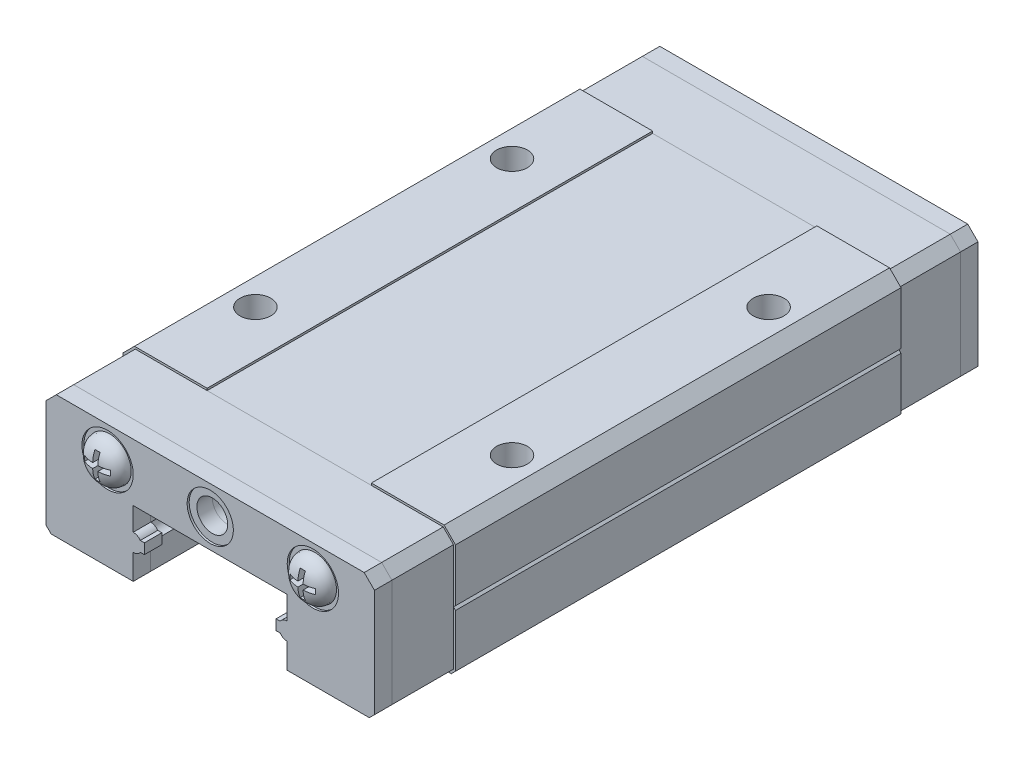
SolidWorks part; units mm, degrees
ref_plane "Front" through (0, 0, 0) normal (0, 0, 1) x (1, 0, 0)
ref_plane "Top" through (0, 0, 0) normal (0, 1, 0) x (1, 0, 0)
ref_plane "Right" through (0, 0, 0) normal (1, 0, 0) x (0, 0, -1)
sketch "Sketch1" plane through (0, 0, 0) normal (0, 0, 1) x (1, 0, 0)
  line L0 (15, 6) -> (-15, 6)
  line L1 (-16, -6) -> (16, -6) construction
  line L2 (-16, -6) -> (-16, 6) construction
  line L3 (-16, 6) -> (16, 6) construction
  line L4 (16, -6) -> (16, 6) construction
  line L5 (-16, -6) -> (16, 6) construction
  line L6 (-16, 6) -> (16, -6) construction
  line L7 (-16, 5) -> (-16, -5.5)
  line L8 (-15.5, -6) -> (-7.5, -6)
  line L9 (-7.5, -6) -> (-7.5, -3.55)
  line L10 (-7.5, 0.4) -> (7.5, 0.4)
  line L11 (-7.5, -1.85) -> (-7.5, 0.4)
  line L12 (0, 0) -> (0, 6) construction
  line L13 (16, -6) -> (16, 6) construction
  line L14 (-6.4126, -2.2) -> (-6.8126, -2.2)
  line L15 (-6.4126, -2.2) -> (-6.4126, -3.2)
  line L16 (-6.4126, -3.2) -> (-6.8126, -3.2)
  line L17 (6.4126, -3.2) -> (6.8126, -3.2)
  line L18 (6.4126, -2.2) -> (6.4126, -3.2)
  line L19 (6.4126, -2.2) -> (6.8126, -2.2)
  line L20 (7.5, -1.85) -> (7.5, 0.4)
  line L21 (7.5, -6) -> (7.5, -3.55)
  line L22 (15.5, -6) -> (7.5, -6)
  line L23 (16, 5) -> (16, -5.5)
  line L24 (-15, 6) -> (-16, 5)
  line L25 (-16, -5.5) -> (-15.5, -6)
  line L26 (15, 6) -> (16, 5)
  line L27 (16, -5.5) -> (15.5, -6)
  arc A0 (-7.5, -3.55) -> (-6.8126, -3.2) centre (-7.5, -2.7) ccw
  arc A1 (-6.8126, -2.2) -> (-7.5, -1.85) centre (-7.5, -2.7) ccw
  arc A2 (6.8126, -2.2) -> (7.5, -1.85) centre (7.5, -2.7) cw
  arc A3 (7.5, -3.55) -> (6.8126, -3.2) centre (7.5, -2.7) cw
  point P0 (0, 0)
  point P26 (0, 0.4)
  dimension "D4" = 1.7
  dimension "D1" = 12
  dimension "D2" = 32
  dimension "D3" = 8.5
  dimension "D5" = 3.3
  dimension "D6" = 0.5
  dimension "D7" = 0.5
  dimension "D8" = 0.4
  dimension "D9" = 6.4
extrude "Boss-Extrude1" add sketch "Sketch1" along normal blind 1.7
sketch "Sketch2" plane through (0, 0, 0) normal (0, 0, -1) x (-1, 0, 0)
  line L20 (7.5, 0.4) -> (7.5, -1.85)
  line L21 (6.8126, -2.2) -> (6.4126, -2.2)
  line L22 (6.4126, -2.2) -> (6.4126, -3.2)
  line L23 (6.4126, -3.2) -> (6.8126, -3.2)
  line L24 (7.5, -3.55) -> (7.5, -6)
  line L25 (7.5, -6) -> (15.5, -6)
  line L26 (15.5, -6) -> (16, -5.5)
  line L27 (16, -5.5) -> (16, 5)
  line L28 (16, 5) -> (15, 6)
  line L29 (15, 6) -> (-15, 6)
  line L30 (-15, 6) -> (-16, 5)
  line L31 (-16, 5) -> (-16, -5.5)
  line L32 (-16, -5.5) -> (-15.5, -6)
  line L33 (-15.5, -6) -> (-7.5, -6)
  line L34 (-7.5, -6) -> (-7.5, -3.55)
  line L35 (-6.8126, -3.2) -> (-6.4126, -3.2)
  line L36 (-6.4126, -3.2) -> (-6.4126, -2.2)
  line L37 (-6.4126, -2.2) -> (-6.8126, -2.2)
  line L38 (-7.5, -1.85) -> (-7.5, 0.4)
  line L39 (-7.5, 0.4) -> (7.5, 0.4)
  line L40 (7.5, 0.4) -> (7.5, -1.85)
  line L41 (6.8126, -2.2) -> (6.4126, -2.2)
  line L42 (6.4126, -2.2) -> (6.4126, -3.2)
  line L43 (6.4126, -3.2) -> (6.8126, -3.2)
  line L44 (7.5, -3.55) -> (7.5, -6)
  line L45 (7.5, -6) -> (15.5, -6)
  line L46 (15.5, -6) -> (16, -5.5)
  line L47 (16, -5.5) -> (16, 5)
  line L48 (16, 5) -> (15, 6)
  line L49 (15, 6) -> (-15, 6)
  line L50 (-15, 6) -> (-16, 5)
  line L51 (-16, 5) -> (-16, -5.5)
  line L52 (-16, -5.5) -> (-15.5, -6)
  line L53 (-15.5, -6) -> (-7.5, -6)
  line L54 (-7.5, -6) -> (-7.5, -3.55)
  line L55 (-6.8126, -3.2) -> (-6.4126, -3.2)
  line L56 (-6.4126, -3.2) -> (-6.4126, -2.2)
  line L57 (-6.4126, -2.2) -> (-6.8126, -2.2)
  line L58 (-7.5, -1.85) -> (-7.5, 0.4)
  line L59 (-7.5, 0.4) -> (7.5, 0.4)
  circle A0 centre (-7.5, -2.7) radius 0.85
  circle A1 centre (7.5, -2.7) radius 0.85
  arc A4 (7.5, -1.85) -> (6.8126, -2.2) centre (7.5, -2.7) ccw
  arc A5 (6.8126, -3.2) -> (7.5, -3.55) centre (7.5, -2.7) ccw
  arc A6 (-7.5, -3.55) -> (-6.8126, -3.2) centre (-7.5, -2.7) ccw
  arc A7 (-6.8126, -2.2) -> (-7.5, -1.85) centre (-7.5, -2.7) ccw
  arc A8 (7.5, -1.85) -> (6.8126, -2.2) centre (7.5, -2.7) ccw
  arc A9 (6.8126, -3.2) -> (7.5, -3.55) centre (7.5, -2.7) ccw
  arc A10 (-7.5, -3.55) -> (-6.8126, -3.2) centre (-7.5, -2.7) ccw
  arc A11 (-6.8126, -2.2) -> (-7.5, -1.85) centre (-7.5, -2.7) ccw
  line M25 (7.5, 0.4) -> (7.5, -1.85)
  line M31 (7.5, -3.55) -> (7.5, -6)
  line M32 (7.5, -6) -> (15.5, -6)
  line M33 (15.5, -6) -> (16, -5.5)
  line M34 (16, -5.5) -> (16, 5)
  line M35 (16, 5) -> (15, 6)
  line M36 (15, 6) -> (-15, 6)
  line M37 (-15, 6) -> (-16, 5)
  line M38 (-16, 5) -> (-16, -5.5)
  line M39 (-16, -5.5) -> (-15.5, -6)
  line M40 (-15.5, -6) -> (-7.5, -6)
  line M41 (-7.5, -6) -> (-7.5, -3.55)
  line M47 (-7.5, -1.85) -> (-7.5, 0.4)
  line M48 (-7.5, 0.4) -> (7.5, 0.4)
  dimension "D1" = 0
extrude "Boss-Extrude2" add sketch "Sketch2" along normal blind 6 separate body contours A1 A0 M31 M32 M33 M34 M35 M36 M37 M38 M39 M40 M41 M47 M48 M25 region at (0, 0.9516, 0)
sketch "Sketch3" plane through (0, 0, -6) normal (0, 0, -1) x (-1, 0, 0)
  line L14 (-7.5, -6) -> (-15.7828, -6)
  line L15 (-7.5, -6) -> (15.7828, -6)
  line L16 (7.5, -3.55) -> (7.5, -6) construction
  line L17 (7.5, 0.4) -> (7.5, -1.85) construction
  line L18 (-7.5, 0.4) -> (7.5, 0.4) construction
  line L19 (-7.5, -1.85) -> (-7.5, 0.4) construction
  line L20 (-7.5, -6) -> (-7.5, -3.55) construction
  line L21 (7.5, -3.55) -> (7.5, -6)
  line L22 (7.5, 0.4) -> (7.5, -1.85)
  line L23 (-7.5, 0.4) -> (7.5, 0.4)
  line L24 (-7.5, -1.85) -> (-7.5, 0.4)
  line L25 (-7.5, -6) -> (-7.5, -3.55)
  line L28 (7.3, -3.3185) -> (7.3, -6.2)
  line L29 (7.3, -6.2) -> (15.5828, -6.2)
  line L30 (15.5828, -6.2) -> (16.2, -5.5828)
  line L31 (16.2, -5.5828) -> (16.2, 5.0828)
  line L32 (16.2, 5.0828) -> (15.0828, 6.2)
  line L33 (15.0828, 6.2) -> (-15.0828, 6.2)
  line L34 (-15.0828, 6.2) -> (-16.2, 5.0828)
  line L35 (-16.2, 5.0828) -> (-16.2, -5.5828)
  line L36 (-16.2, -5.5828) -> (-15.5828, -6.2)
  line L37 (-15.5828, -6.2) -> (-7.3, -6.2)
  line L38 (-7.3, -6.2) -> (-7.3, -3.3185)
  line L39 (-7.3, -2.0815) -> (-7.3, 0.2)
  line L40 (-7.3, 0.2) -> (7.3, 0.2)
  line L41 (7.3, 0.2) -> (7.3, -2.0815)
  line L42 (7.3, -3.3185) -> (7.3, -6.2)
  line L43 (7.3, -6.2) -> (15.5828, -6.2)
  line L44 (15.5828, -6.2) -> (16.2, -5.5828)
  line L45 (16.2, -5.5828) -> (16.2, 5.0828)
  line L46 (16.2, 5.0828) -> (15.0828, 6.2)
  line L47 (15.0828, 6.2) -> (-15.0828, 6.2)
  line L48 (-15.0828, 6.2) -> (-16.2, 5.0828)
  line L49 (-16.2, 5.0828) -> (-16.2, -5.5828)
  line L50 (-16.2, -5.5828) -> (-15.5828, -6.2)
  line L51 (-15.5828, -6.2) -> (-7.3, -6.2)
  line L52 (-7.3, -6.2) -> (-7.3, -3.3185)
  line L53 (-7.3, -2.0815) -> (-7.3, 0.2)
  line L54 (-7.3, 0.2) -> (7.3, 0.2)
  line L55 (7.3, 0.2) -> (7.3, -2.0815)
  circle A2 centre (-7.5, -2.7) radius 0.85
  circle A3 centre (7.5, -2.7) radius 0.85
  arc A4 (7.3, -3.3185) -> (7.3, -2.0815) centre (7.5, -2.7) ccw
  arc A5 (-7.3, -2.0815) -> (-7.3, -3.3185) centre (-7.5, -2.7) ccw
  arc A6 (7.3, -3.3185) -> (7.3, -2.0815) centre (7.5, -2.7) ccw
  arc A7 (-7.3, -2.0815) -> (-7.3, -3.3185) centre (-7.5, -2.7) ccw
  arc M19 (7.5, -1.85) -> (7.5, -3.55) centre (7.5, -2.7) cw
  line M20 (7.5, -3.55) -> (7.5, -6)
  line M21 (7.5, -6) -> (15.5, -6)
  line M22 (15.5, -6) -> (16, -5.5)
  line M23 (16, -5.5) -> (16, 5)
  line M24 (16, 5) -> (15, 6)
  line M25 (15, 6) -> (-15, 6)
  line M26 (-15, 6) -> (-16, 5)
  line M27 (-16, 5) -> (-16, -5.5)
  line M28 (-16, -5.5) -> (-15.5, -6)
  line M29 (-15.5, -6) -> (-7.5, -6)
  line M30 (-7.5, -6) -> (-7.5, -3.55)
  arc M31 (-7.5, -3.55) -> (-7.5, -1.85) centre (-7.5, -2.7) cw
  line M32 (-7.5, -1.85) -> (-7.5, 0.4)
  line M33 (-7.5, 0.4) -> (7.5, 0.4)
  line M34 (7.5, 0.4) -> (7.5, -1.85)
  dimension "D1" = 0.2
extrude "Boss-Extrude3" add sketch "Sketch3" along normal blind 43.4 separate body contours M34 M19 M20 M21 M22 M23 M24 M25 M26 M27 M28 M29 M30 M31 M32 M33 | L49 L50 L14 L15 L44 L45 L46 L47 L48 M28 M27 M26 M25 M24 M23 M22 region at (0, 0.9516, -6) region at (15.6414, -5.9654, -6)
sketch "Sketch4" plane through (0, 0, -49.4) normal (0, 0, -1) x (-1, 0, 0)
  line L20 (7.5, 0.4) -> (7.5, -1.85)
  line L21 (6.8126, -2.2) -> (6.4126, -2.2)
  line L22 (6.4126, -2.2) -> (6.4126, -3.2)
  line L23 (6.4126, -3.2) -> (6.8126, -3.2)
  line L24 (7.5, -3.55) -> (7.5, -6)
  line L25 (7.5, -6) -> (15.5, -6)
  line L26 (15.5, -6) -> (16, -5.5)
  line L27 (16, -5.5) -> (16, 5)
  line L28 (16, 5) -> (15, 6)
  line L29 (15, 6) -> (-15, 6)
  line L30 (-15, 6) -> (-16, 5)
  line L31 (-16, 5) -> (-16, -5.5)
  line L32 (-16, -5.5) -> (-15.5, -6)
  line L33 (-15.5, -6) -> (-7.5, -6)
  line L34 (-7.5, -6) -> (-7.5, -3.55)
  line L35 (-6.8126, -3.2) -> (-6.4126, -3.2)
  line L36 (-6.4126, -3.2) -> (-6.4126, -2.2)
  line L37 (-6.4126, -2.2) -> (-6.8126, -2.2)
  line L38 (-7.5, -1.85) -> (-7.5, 0.4)
  line L39 (-7.5, 0.4) -> (7.5, 0.4)
  line L40 (7.5, 0.4) -> (7.5, -1.85)
  line L41 (6.8126, -2.2) -> (6.4126, -2.2)
  line L42 (6.4126, -2.2) -> (6.4126, -3.2)
  line L43 (6.4126, -3.2) -> (6.8126, -3.2)
  line L44 (7.5, -3.55) -> (7.5, -6)
  line L45 (7.5, -6) -> (15.5, -6)
  line L46 (15.5, -6) -> (16, -5.5)
  line L47 (16, -5.5) -> (16, 5)
  line L48 (16, 5) -> (15, 6)
  line L49 (15, 6) -> (-15, 6)
  line L50 (-15, 6) -> (-16, 5)
  line L51 (-16, 5) -> (-16, -5.5)
  line L52 (-16, -5.5) -> (-15.5, -6)
  line L53 (-15.5, -6) -> (-7.5, -6)
  line L54 (-7.5, -6) -> (-7.5, -3.55)
  line L55 (-6.8126, -3.2) -> (-6.4126, -3.2)
  line L56 (-6.4126, -3.2) -> (-6.4126, -2.2)
  line L57 (-6.4126, -2.2) -> (-6.8126, -2.2)
  line L58 (-7.5, -1.85) -> (-7.5, 0.4)
  line L59 (-7.5, 0.4) -> (7.5, 0.4)
  circle A0 centre (-7.5, -2.7) radius 0.85
  circle A1 centre (7.5, -2.7) radius 0.85
  arc A4 (7.5, -1.85) -> (6.8126, -2.2) centre (7.5, -2.7) ccw
  arc A5 (6.8126, -3.2) -> (7.5, -3.55) centre (7.5, -2.7) ccw
  arc A6 (-7.5, -3.55) -> (-6.8126, -3.2) centre (-7.5, -2.7) ccw
  arc A7 (-6.8126, -2.2) -> (-7.5, -1.85) centre (-7.5, -2.7) ccw
  arc A8 (7.5, -1.85) -> (6.8126, -2.2) centre (7.5, -2.7) ccw
  arc A9 (6.8126, -3.2) -> (7.5, -3.55) centre (7.5, -2.7) ccw
  arc A10 (-7.5, -3.55) -> (-6.8126, -3.2) centre (-7.5, -2.7) ccw
  arc A11 (-6.8126, -2.2) -> (-7.5, -1.85) centre (-7.5, -2.7) ccw
  dimension "D1" = 0
extrude "Boss-Extrude4" add sketch "Sketch4" along normal blind 6 separate body contours L49 L50 L51 L52 L53 L54 A10 L55 L56 L57 A11 L58 L59 L40 A8 L41 L42 L43 A9 L44 L45 L46 L47 L48
sketch "Sketch5" plane through (0, 0, -55.4) normal (0, 0, -1) x (-1, 0, 0)
  line L20 (7.5, 0.4) -> (7.5, -1.85)
  line L21 (-7.5, 0.4) -> (7.5, 0.4)
  line L22 (-7.5, -1.85) -> (-7.5, 0.4)
  line L23 (-6.4126, -2.2) -> (-6.8126, -2.2)
  line L24 (-6.4126, -3.2) -> (-6.4126, -2.2)
  line L25 (-6.8126, -3.2) -> (-6.4126, -3.2)
  line L26 (-7.5, -6) -> (-7.5, -3.55)
  line L27 (-15.5, -6) -> (-7.5, -6)
  line L28 (-16, -5.5) -> (-15.5, -6)
  line L29 (-16, 5) -> (-16, -5.5)
  line L30 (-15, 6) -> (-16, 5)
  line L31 (15, 6) -> (-15, 6)
  line L32 (16, 5) -> (15, 6)
  line L33 (16, -5.5) -> (16, 5)
  line L34 (15.5, -6) -> (16, -5.5)
  line L35 (7.5, -6) -> (15.5, -6)
  line L36 (7.5, -3.55) -> (7.5, -6)
  line L37 (6.4126, -3.2) -> (6.8126, -3.2)
  line L38 (6.4126, -2.2) -> (6.4126, -3.2)
  line L39 (6.8126, -2.2) -> (6.4126, -2.2)
  line L40 (7.5, 0.4) -> (7.5, -1.85)
  line L41 (-7.5, 0.4) -> (7.5, 0.4)
  line L42 (-7.5, -1.85) -> (-7.5, 0.4)
  line L43 (-6.4126, -2.2) -> (-6.8126, -2.2)
  line L44 (-6.4126, -3.2) -> (-6.4126, -2.2)
  line L45 (-6.8126, -3.2) -> (-6.4126, -3.2)
  line L46 (-7.5, -6) -> (-7.5, -3.55)
  line L47 (-15.5, -6) -> (-7.5, -6)
  line L48 (-16, -5.5) -> (-15.5, -6)
  line L49 (-16, 5) -> (-16, -5.5)
  line L50 (-15, 6) -> (-16, 5)
  line L51 (15, 6) -> (-15, 6)
  line L52 (16, 5) -> (15, 6)
  line L53 (16, -5.5) -> (16, 5)
  line L54 (15.5, -6) -> (16, -5.5)
  line L55 (7.5, -6) -> (15.5, -6)
  line L56 (7.5, -3.55) -> (7.5, -6)
  line L57 (6.4126, -3.2) -> (6.8126, -3.2)
  line L58 (6.4126, -2.2) -> (6.4126, -3.2)
  line L59 (6.8126, -2.2) -> (6.4126, -2.2)
  arc A4 (-6.8126, -2.2) -> (-7.5, -1.85) centre (-7.5, -2.7) ccw
  arc A5 (-7.5, -3.55) -> (-6.8126, -3.2) centre (-7.5, -2.7) ccw
  arc A6 (6.8126, -3.2) -> (7.5, -3.55) centre (7.5, -2.7) ccw
  arc A7 (7.5, -1.85) -> (6.8126, -2.2) centre (7.5, -2.7) ccw
  arc A8 (-6.8126, -2.2) -> (-7.5, -1.85) centre (-7.5, -2.7) ccw
  arc A9 (-7.5, -3.55) -> (-6.8126, -3.2) centre (-7.5, -2.7) ccw
  arc A10 (6.8126, -3.2) -> (7.5, -3.55) centre (7.5, -2.7) ccw
  arc A11 (7.5, -1.85) -> (6.8126, -2.2) centre (7.5, -2.7) ccw
  dimension "D1" = 0
extrude "Boss-Extrude5" add sketch "Sketch5" along normal blind 1.7 separate body
sketch "Sketch6" plane through (0, 0, -49.4) normal (0, 0, -1) x (-1, 0, 0)
  line L0 (-16.2, -0.25) -> (-16, -0.25) construction
  line L1 (-16.2, 5.0828) -> (-16.2, -5.5828) construction
  line L2 (-16, 5) -> (-16, -5.5) construction
  line L3 (-16, -0.25) -> (-16.2, -0.05)
  line L4 (-16, -0.25) -> (-16.2, -0.45)
  line L5 (-16.2, -0.05) -> (-16.2, -0.45)
  dimension "D1" = 45
extrude "Cut-Extrude3" cut sketch "Sketch6" against normal up to next (43.4 mm away)
sketch "Sketch8" plane through (0, 6.2, 0) normal (0, 1, 0) x (1, 0, 0)
  line L0 (-15.0828, 49.4) -> (15.0828, 49.4) construction
  line L1 (-8, 49.4) -> (8, 49.4)
  line L2 (-8, 49.4) -> (-8, 6)
  line L3 (-8, 6) -> (8, 6)
  line L4 (8, 49.4) -> (8, 6)
  line L5 (-8, 49.4) -> (8, 6) construction
  line L6 (-8, 6) -> (8, 49.4) construction
  line L7 (-15.0828, 6) -> (15.0828, 6) construction
  point P4 (0, 27.7)
  dimension "D1" = 16
extrude "Cut-Extrude4" cut sketch "Sketch8" against normal blind 0.2
mirror "Mirror1" about plane through (0, 0, 0) normal (1, 0, 0) of "Cut-Extrude3"
sketch "Sketch9" plane through (0, 6.2, 0) normal (0, 1, 0) x (1, 0, 0)
  line L1 (-16.2, 27.7) -> (16.2, 27.7) construction
  line L3 (-16.2, 49.4) -> (-16.2, 6) construction
  line L4 (16.2, 49.4) -> (16.2, 6) construction
  line L6 (-12.5, 15.2) -> (12.5, 15.2) construction
  line L7 (-12.5, 15.2) -> (-12.5, 40.2) construction
  line L8 (-12.5, 40.2) -> (12.5, 40.2) construction
  line L9 (12.5, 15.2) -> (12.5, 40.2) construction
  line L10 (-12.5, 15.2) -> (12.5, 40.2) construction
  line L11 (-12.5, 40.2) -> (12.5, 15.2) construction
  circle A4 centre (12.5, 40.2) radius 1.5
  circle A5 centre (-12.5, 40.2) radius 1.5
  circle A6 centre (-12.5, 15.2) radius 1.5
  circle A7 centre (12.5, 15.2) radius 1.5
  point P6 (0, 27.7)
  dimension "D1" = 25
  dimension "D3" = 3
  dimension "D4" = 3
  dimension "D5" = 3
  dimension "D2" = 3
extrude "Cut-Extrude5" cut sketch "Sketch9" against normal blind 5.8
sketch "Sketch10" plane through (0, 0, -57.1) normal (0, 0, -1) x (-1, 0, 0)
  line L0 (15, 6) -> (-15, 6) construction
  line L1 (-16, 5) -> (-16, -5.5) construction
  line L2 (16, -5.5) -> (16, 5) construction
  line L4 (0, 0.4) -> (0, 6) construction
  line L5 (-7.5, 0.4) -> (7.5, 0.4) construction
  line L6 (-8, 6) -> (8, 6) construction
  circle A0 centre (-10, 3) radius 2.5
  circle A1 centre (10, 3) radius 2.5
  circle A3 centre (0, 3.2) radius 2.25
  dimension "D1" = 5
  dimension "D4" = 5
  dimension "D5" = 6
  dimension "D7" = 4.5
  dimension "D2" = 3
  dimension "D3" = 6
  dimension "D6" = 3
extrude "Cut-Extrude6" cut sketch "Sketch10" against normal blind 0.2
sketch "Sketch11" plane through (0, 0, -56.9) normal (0, 0, -1) x (-1, 0, 0)
  circle A0 centre (0, 3.2) radius 1.5
  dimension "D1" = 3
extrude "Cut-Extrude7" cut sketch "Sketch11" against normal blind 5.8
sketch "Sketch12" plane through (0, 0, -56.9) normal (0, 0, -1) x (-1, 0, 0)
  circle A0 centre (-10, 3) radius 2.1
  dimension "D1" = 4.2
extrude "Boss-Extrude7" add sketch "Sketch12" along normal blind 1.4
fillet "Fillet1" radius 1.4 1 edges at (7.9, 3, -58.3) second distance 1.8 first distance on face at (7.9, 3, -58.3)
sketch "Sketch14" plane through (0, 0, -58.3) normal (0, 0, -1) x (-1, 0, 0)
  line L0 (-9.7, 3) -> (-10.3, 3) construction
  line L2 (-10.25, 1.75) -> (-9.75, 1.75)
  line L3 (-10.25, 1.75) -> (-10.25, 4.25)
  line L4 (-10.25, 4.25) -> (-9.75, 4.25)
  line L5 (-9.75, 1.75) -> (-9.75, 4.25)
  line L6 (-10.25, 1.75) -> (-9.75, 4.25) construction
  line L7 (-10.25, 4.25) -> (-9.75, 1.75) construction
  line L8 (-11.25, 2.75) -> (-8.75, 2.75)
  line L9 (-11.25, 2.75) -> (-11.25, 3.25)
  line L10 (-11.25, 3.25) -> (-8.75, 3.25)
  line L11 (-8.75, 2.75) -> (-8.75, 3.25)
  line L12 (-11.25, 2.75) -> (-8.75, 3.25) construction
  line L13 (-11.25, 3.25) -> (-8.75, 2.75) construction
  spline S1 degree 3 poles (-9.7156, 2.8822) (-9.6922, 3) (-9.7156, 3.1178) (-9.7823, 3.2177) (-9.8822, 3.2844) (-10, 3.3078) (-10.1178, 3.2844) (-10.2177, 3.2177) (-10.2844, 3.1178) (-10.3078, 3) (-10.2844, 2.8822) (-10.2177, 2.7823) (-10.1178, 2.7156) (-10, 2.6922) (-9.8822, 2.7156) (-9.7823, 2.7823) (-9.7156, 2.8822) (-9.6922, 3) (-9.7156, 3.1178) knots -0.1875 -0.125 -0.0625 0 0.0625 0.125 0.1875 0.25 0.3125 0.375 0.4375 0.5 0.5625 0.625 0.6875 0.75 0.8125 0.875 0.9375 1 1.0625 1.125 1.1875 only from (-9.7, 3) to (-9.7, 3)
  spline S2 degree 3 poles (-9.7156, 2.8822) (-9.6922, 3) (-9.7156, 3.1178) (-9.7823, 3.2177) (-9.8822, 3.2844) (-10, 3.3078) (-10.1178, 3.2844) (-10.2177, 3.2177) (-10.2844, 3.1178) (-10.3078, 3) (-10.2844, 2.8822) (-10.2177, 2.7823) (-10.1178, 2.7156) (-10, 2.6922) (-9.8822, 2.7156) (-9.7823, 2.7823) (-9.7156, 2.8822) (-9.6922, 3) (-9.7156, 3.1178) knots -0.1875 -0.125 -0.0625 0 0.0625 0.125 0.1875 0.25 0.3125 0.375 0.4375 0.5 0.5625 0.625 0.6875 0.75 0.8125 0.875 0.9375 1 1.0625 1.125 1.1875 only from (-9.7, 3) to (-9.7, 3) construction
  point P1 (-10, 3)
  point P7 (-10, 3)
  dimension "D2" = 2.5
  dimension "D3" = 0.5
  dimension "D4" = 0.5
  dimension "D5" = 2.5
  dimension "D1" = 0
extrude "Cut-Extrude8" cut sketch "Sketch14" against normal blind 1 contours L3 L8 | L8 | L8 L5 | L5 | L10 | L10 L5 | L10 L3 | L10 L3 L8 L5 | L3 | L10 L9 L8 L3 | L8 L11 L10 L5 | L3 L10 L5 L4 | L8 L3 L2 L5 region at (10, 2.239, -58.3) region at (10.761, 3, -58.3) region at (10.2238, 2.7762, -58.3) region at (9.7762, 2.7762, -58.3) region at (9.239, 3, -58.3) region at (10.2701, 3, -58.3) region at (10, 3, -58.3) region at (10, 2.7299, -58.3) region at (9.7299, 3, -58.3) region at (10.2238, 3.2238, -58.3) region at (9.7762, 3.2238, -58.3) region at (10, 3.761, -58.3) region at (10, 3.2701, -58.3)
mirror "Mirror2" about plane through (0, 0, 0) normal (1, 0, 0) of "Fillet1", "Cut-Extrude8", "Boss-Extrude7"
ref_plane "Plane1" through (0, 0, -27.7) normal (0, 0, -1) x (-1, 0, 0)
mirror "Mirror3" about plane through (0, 0, -27.7) normal (0, 0, -1) of "Cut-Extrude7", "Cut-Extrude6"
sketch "Sketch16" plane through (0, 0, 1.5) normal (0, 0, 1) x (1, 0, 0)
  circle A0 centre (10, 3) radius 2.1
  dimension "D1" = 4.2
extrude "Boss-Extrude8" add sketch "Sketch16" along normal blind 1.4
fillet "Fillet2" radius 1.4 1 edges at (12.1, 3, 2.9) second distance 1.8 first distance on face at (12.1, 3, 2.9)
sketch "Sketch17" plane through (0, 0, 2.9) normal (0, 0, 1) x (1, 0, 0)
  line L12 (10.25, 3.25) -> (10.25, 4.25)
  line L13 (11.25, 3.25) -> (10.25, 3.25)
  line L14 (11.25, 2.75) -> (11.25, 3.25)
  line L15 (10.25, 2.75) -> (11.25, 2.75)
  line L16 (10.25, 1.75) -> (10.25, 2.75)
  line L17 (9.75, 1.75) -> (10.25, 1.75)
  line L18 (9.75, 2.75) -> (9.75, 1.75)
  line L19 (8.75, 2.75) -> (9.75, 2.75)
  line L20 (8.75, 3.25) -> (8.75, 2.75)
  line L21 (9.75, 3.25) -> (8.75, 3.25)
  line L22 (9.75, 4.25) -> (9.75, 3.25)
  line L23 (10.25, 4.25) -> (9.75, 4.25)
  line L24 (10.25, 3.25) -> (10.25, 4.25)
  line L25 (11.25, 3.25) -> (10.25, 3.25)
  line L26 (11.25, 2.75) -> (11.25, 3.25)
  line L27 (10.25, 2.75) -> (11.25, 2.75)
  line L28 (10.25, 1.75) -> (10.25, 2.75)
  line L29 (9.75, 1.75) -> (10.25, 1.75)
  line L30 (9.75, 2.75) -> (9.75, 1.75)
  line L31 (8.75, 2.75) -> (9.75, 2.75)
  line L32 (8.75, 3.25) -> (8.75, 2.75)
  line L33 (9.75, 3.25) -> (8.75, 3.25)
  line L34 (9.75, 4.25) -> (9.75, 3.25)
  line L35 (10.25, 4.25) -> (9.75, 4.25)
  dimension "D1" = 0
extrude "Cut-Extrude9" cut sketch "Sketch17" against normal blind 1
mirror "Mirror7" about plane through (0, 0, 0) normal (1, 0, 0) of "Fillet2", "Cut-Extrude9", "Boss-Extrude8"
